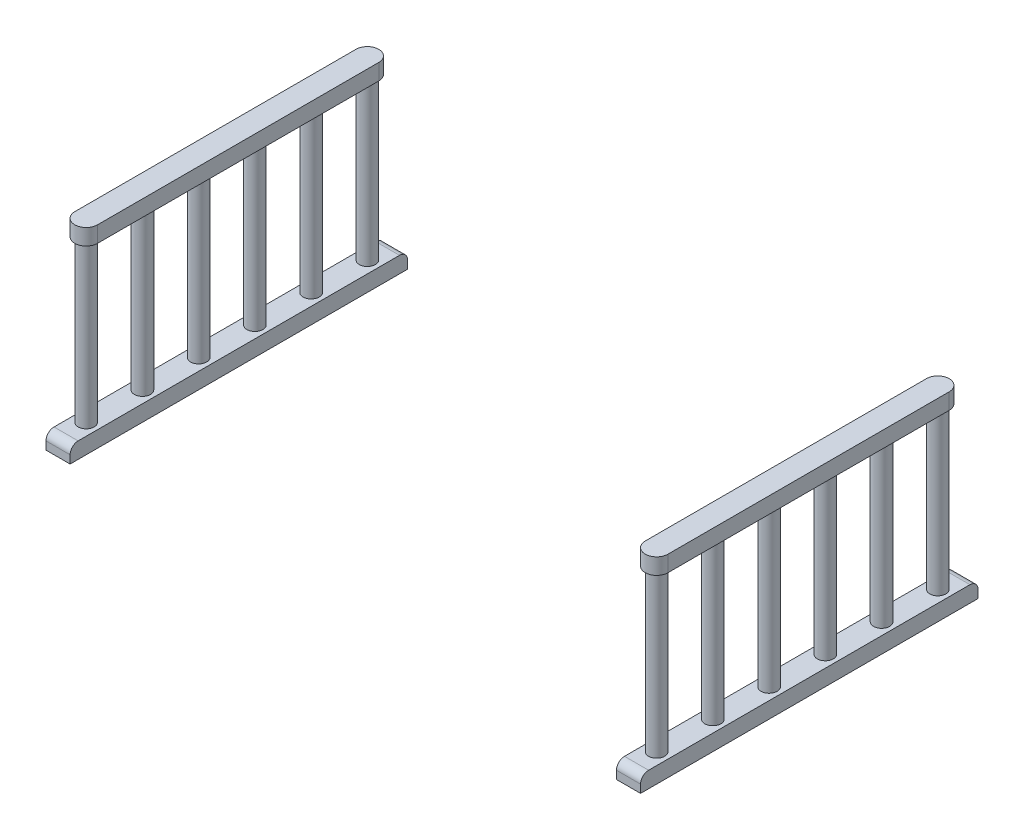
SolidWorks part; units mm, degrees
ref_plane "Front Plane" through (0, 0, 0) normal (0, 0, 1) x (1, 0, 0)
ref_plane "Top Plane" through (0, 0, 0) normal (0, 1, 0) x (1, 0, 0)
ref_plane "Right Plane" through (0, 0, 0) normal (1, 0, 0) x (0, 0, -1)
sketch "Sketch2" plane through (0, 0, 0) normal (0, 1, 0) x (1, 0, 0)
  line L0 (0, -12.024) -> (0, 987.976) construction
  line L1 (-1850, -12.024) -> (1850, -12.024) construction
  line L2 (1850, -12.024) -> (1700, -12.024)
  line L3 (-1850, -12.024) -> (-1700, -12.024)
  line L4 (-1850, -12.024) -> (-1850, 2087.976)
  line L5 (-1850, 2087.976) -> (-1700, 2087.976)
  line L6 (-1700, -12.024) -> (-1700, 2087.976)
  line L7 (1850, 2087.976) -> (1700, 2087.976)
  line L8 (1850, -12.024) -> (1850, 2087.976)
  line L9 (1700, -12.024) -> (1700, 2087.976)
  dimension "D1" = 1000
  dimension "D2" = 1850
  dimension "D3" = 2100
  dimension "D4" = 150
extrude "Boss-Extrude3" add sketch "Sketch2" along normal blind 100
ref_plane "Plane1" through (0, 100, 0) normal (0, 1, 0) x (1, 0, 0)
sketch "Sketch3" plane through (0, 100, 0) normal (0, 1, 0) x (1, 0, 0)
  line L0 (0, 0) -> (0, 2142.9852) construction
  line L1 (-1775, -12.024) -> (-1775, 162.976) construction
  line L2 (-1850, -12.024) -> (-1700, -12.024) construction
  circle A0 centre (-1775, 162.976) radius 50
  dimension "D2" = 100
  dimension "D1" = 175
extrude "Boss-Extrude4" add sketch "Sketch3" along normal blind 1000
pattern_linear "LPattern1" count 6 spacing 350 along (0, 0, -1) of "Boss-Extrude4"
ref_plane "Plane2" through (1700, 100, 12.024) normal (1, 0, 0) x (0, 0, -1)
sketch "Sketch5" plane through (0, 100, 0) normal (0, 1, 0) x (1, 0, 0)
  line L0 (1775, 2087.976) -> (1775, 1912.976) construction
  line L1 (1850, 2087.976) -> (1700, 2087.976) construction
  circle A0 centre (1775, 1912.976) radius 50
  dimension "D2" = 100
  dimension "D1" = 175
extrude "Boss-Extrude5" add sketch "Sketch5" along normal blind 1000
pattern_linear "LPattern2" count 6 spacing 350 along (0, 0, 1) of "Boss-Extrude5"
ref_plane "Plane3" through (0, 1100, 0) normal (0, 1, 0) x (1, 0, 0)
fillet "Fillet1" radius 50 1 edges at (-1775, 100, -2087.976)
fillet "Fillet2" radius 50 1 edges at (-1775, 100, 12.024)
fillet "Fillet3" radius 50 1 edges at (1775, 100, 12.024)
fillet "Fillet4" radius 50 1 edges at (1775, 100, -2087.976)
sketch "Sketch13" plane through (0, 1100, 0) normal (0, 1, 0) x (1, 0, 0)
  line L0 (-1775, 162.976) -> (-1775, 1912.976) construction
  line L1 (-1845.8383, 162.976) -> (-1845.8383, 1912.976)
  line L2 (-1704.1617, 162.976) -> (-1704.1617, 1912.976)
  line L3 (0, 0) -> (0, 2341.2867) construction
  line L4 (0, -605) -> (0, 605) construction
  line L5 (1775, 162.976) -> (1775, 1912.976) construction
  line L6 (1845.8383, 162.976) -> (1845.8383, 1912.976)
  line L7 (1704.1617, 162.976) -> (1704.1617, 1912.976)
  arc A0 (-1845.8383, 162.976) -> (-1704.1617, 162.976) centre (-1775, 162.976) ccw
  arc A1 (-1704.1617, 1912.976) -> (-1845.8383, 1912.976) centre (-1775, 1912.976) ccw
  arc A2 (1845.8383, 162.976) -> (1704.1617, 162.976) centre (1775, 162.976) cw
  arc A3 (1704.1617, 1912.976) -> (1845.8383, 1912.976) centre (1775, 1912.976) cw
  point P4 (-1775, 1037.976)
  point P16 (1775, 1037.976)
extrude "Boss-Extrude8" add sketch "Sketch13" along normal blind 100
